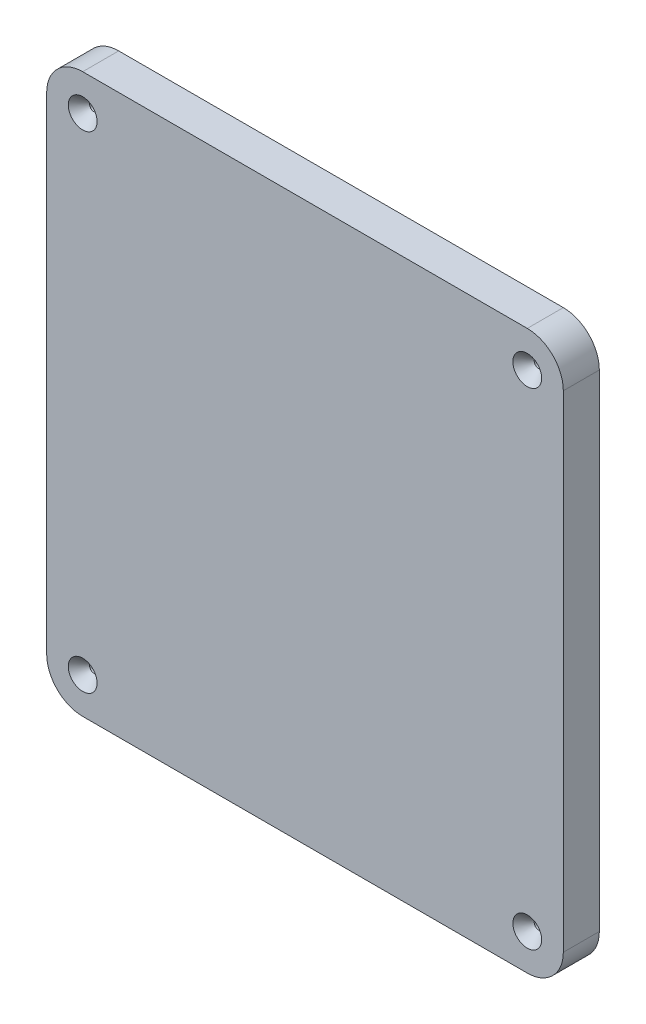
SolidWorks part; units mm, degrees
material "Beech"
ref_plane "Front Plane" through (0, 0, 0) normal (0, 0, 1) x (1, 0, 0)
ref_plane "Top Plane" through (0, 0, 0) normal (0, 1, 0) x (1, 0, 0)
ref_plane "Right Plane" through (0, 0, 0) normal (1, 0, 0) x (0, 0, -1)
sketch "Sketch1" plane through (0, 0, 0) normal (0, 0, 1) x (1, 0, 0)
  line L0 (139.05, 899.8522) -> (139.05, 151.949) construction
  line L1 (-43.1, 899.8522) -> (-43.1, 151.949) construction
  line L2 (-43.1, 906.2022) -> (139.05, 906.2022) construction
  line L8 (139.05, 668.0772) -> (139.05, 864.9272)
  line L9 (139.05, 864.9272) -> (-43.1, 864.9272)
  line L10 (-43.1, 864.9272) -> (-43.1, 668.0772)
  line L11 (-43.1, 668.0772) -> (139.05, 668.0772)
  dimension "D1" = 196.85
  dimension "D2" = 41.275
extrude "Boss-Extrude1" add sketch "Sketch1" along normal blind 12.7
fillet "Fillet1" radius 12.7 4 edges at (139.05, 864.9272, 6.35) (139.05, 668.0772, 6.35) (-43.1, 668.0772, 6.35) (-43.1, 864.9272, 6.35)
hole_wizard "Hole1" positions "Sketch2" profile "Sketch3" legacy
sketch "Sketch2" plane through (47.975, -457.9606, 12.7) normal (0, 0, 1) x (1, 0, 0)
  point P0 (-78.375, 1310.1878)
  point P3 (-78.375, 1138.7378)
  point P6 (78.375, 1138.7378)
  point P9 (78.375, 1310.1878)
sketch "Sketch3" plane through (-30.4, 852.2272, 12.7) normal (1, 0, 0) x (0, -1, 0)
  line L0 (0, 0) -> (0, 32.7039)
  line L1 (0, 32.7039) -> (1.5875, 31.75)
  line L2 (1.5875, 31.75) -> (1.5875, 4.0177)
  line L3 (1.5875, 4.0177) -> (5.08, 0)
  line L4 (5.08, 0) -> (0, 0)
  line L5 (0, -14.3089) -> (0, 102.4216) construction
  line L6 (0, 32.7039) -> (-1.5875, 31.75) construction
  line L7 (-1.5875, 4.0177) -> (-5.08, 0) construction
  dimension "Diameter" = 3.175
  dimension "Depth" = 31.75
  dimension "C-Sink Diameter" = 10.16
  dimension "C-Sink Angle" = 82
  dimension "Drill Angle" = 118
